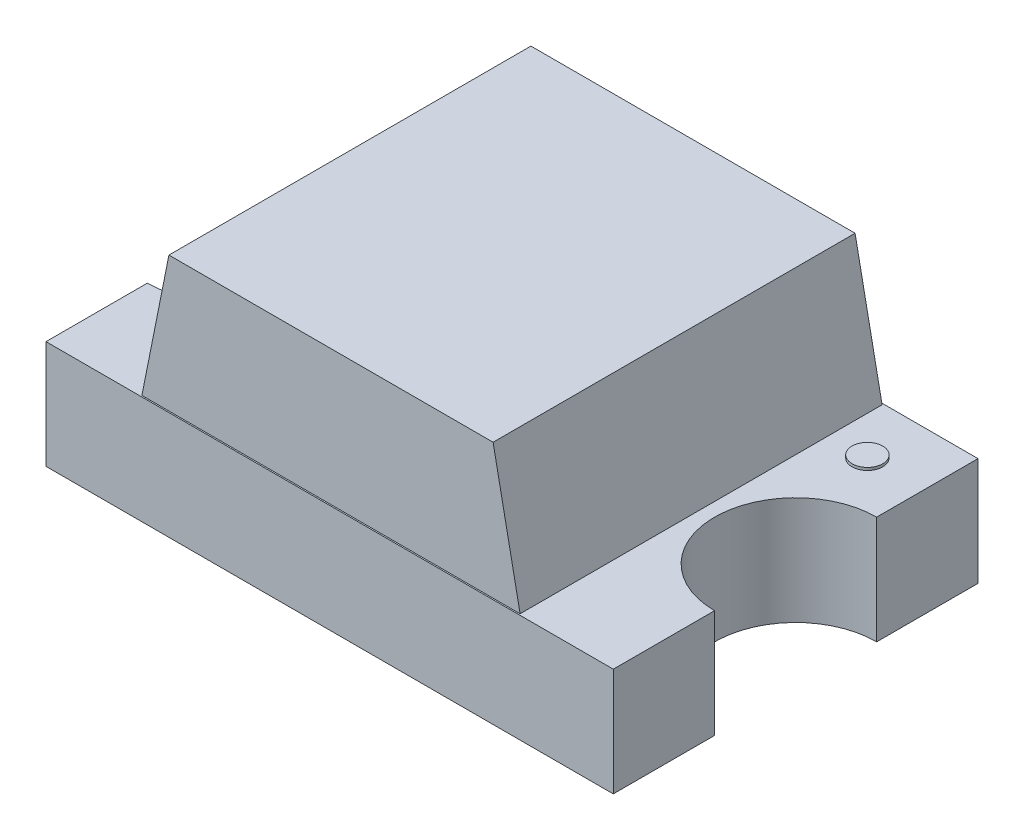
SolidWorks part; units mm, degrees
ref_plane "Front Plane" through (0, 0, 0) normal (0, 0, 1) x (1, 0, 0)
ref_plane "Top Plane" through (0, 0, 0) normal (0, 1, 0) x (1, 0, 0)
ref_plane "Right Plane" through (0, 0, 0) normal (1, 0, 0) x (0, 0, -1)
sketch "Sketch1" plane through (0, 0, 0) normal (0, 1, 0) x (1, 0, 0)
  line L0 (0, 0) -> (1.05, 0) construction
  line L1 (-1.05, -0.675) -> (1.05, -0.675)
  line L2 (0, 0.74) -> (0, -0.7533) construction
  line L3 (-1.05, 0.675) -> (1.05, 0.675)
  line L4 (1.05, 0.3) -> (1.05, 0.675)
  line L5 (-1.05, -0.675) -> (1.05, 0.675) construction
  line L6 (-1.05, 0.675) -> (1.05, -0.675) construction
  line L7 (1.05, -0.675) -> (1.05, -0.3)
  line L8 (-1.05, -0.675) -> (-1.05, -0.3)
  line L9 (-1.05, 0.3) -> (-1.05, 0.675)
  arc A0 (1.05, 0.3) -> (1.05, -0.3) centre (1.05, 0) ccw
  arc A1 (-1.05, 0.3) -> (-1.05, -0.3) centre (-1.05, 0) cw
  dimension "D1" = 2.1
  dimension "D2" = 1.35
extrude "Boss-Extrude1" add sketch "Sketch1" along normal blind 0.4
sketch "Sketch2" plane through (0, 0.4, 0) normal (0, 1, 0) x (1, 0, 0)
  line L1 (-0.7, -0.67) -> (0.7, -0.67)
  line L2 (-0.7, -0.67) -> (-0.7, 0.67)
  line L3 (-0.7, 0.67) -> (0.7, 0.67)
  line L4 (0.7, -0.67) -> (0.7, 0.67)
  line L5 (-0.7, -0.67) -> (0.7, 0.67) construction
  line L6 (-0.7, 0.67) -> (0.7, -0.67) construction
  point P0 (0, 0)
  dimension "D1" = 1.34
  dimension "D2" = 1.4
extrude "Boss-Extrude2" add sketch "Sketch2" along normal blind 0.5 separate body
chamfer "Chamfer1" distance 0.5 distance2 0.1 2 edges at (0.7, 0.9, 0) (-0.7, 0.9, 0) tangent propagation no first distance on face at (0.7, 0.65, 0) first distance on face at (-0.7, 0.65, 0)
sketch "Sketch3" plane through (0, 0.4, 0) normal (0, 1, 0) x (1, 0, 0)
  circle A0 centre (0.8434, 0.4722) radius 0.0568
extrude "Boss-Extrude3" add sketch "Sketch3" along normal blind 0.01
